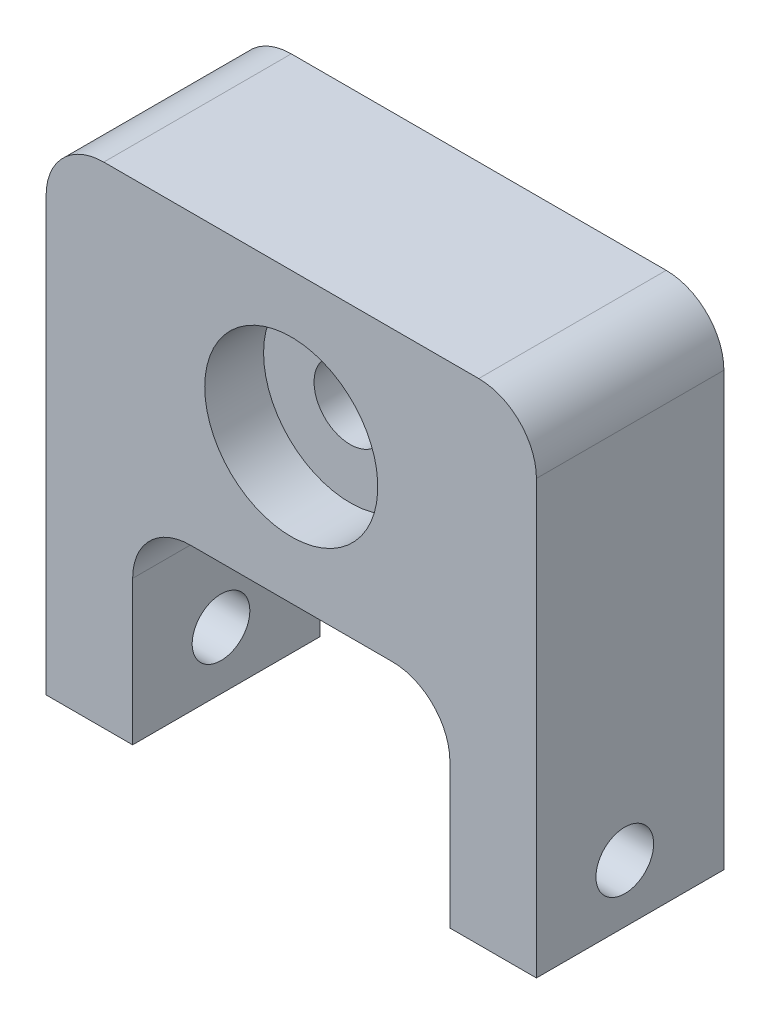
SolidWorks part; units mm, degrees
material "1060 Alloy"
ref_plane "Front" through (0, 0, 0) normal (0, 0, 1) x (1, 0, 0)
ref_plane "Top" through (0, 0, 0) normal (0, 1, 0) x (1, 0, 0)
ref_plane "Right" through (0, 0, 0) normal (1, 0, 0) x (0, 0, -1)
sketch "Sketch1" plane through (0, 0, 0) normal (0, 0, 1) x (1, 0, 0)
  line L1 (26.9875, -15.875) -> (-26.9875, -15.875)
  line L2 (26.9875, -15.875) -> (26.9875, 15.875)
  line L3 (26.9875, 15.875) -> (-26.9875, 15.875)
  line L4 (-26.9875, -15.875) -> (-26.9875, 15.875)
  line L5 (26.9875, -15.875) -> (-26.9875, 15.875) construction
  line L6 (26.9875, 15.875) -> (-26.9875, -15.875) construction
  point P0 (0, 0)
  dimension "D1" = 31.75
  dimension "D2" = 53.975
extrude "Boss-Extrude1" add sketch "Sketch1" along normal blind 20.6375
sketch "Sketch2" plane through (0, 0, 0) normal (0, 0, -1) x (-1, 0, 0)
  circle A0 centre (0, 0) radius 11.1125
  dimension "D1" = 22.225
extrude "Cut-Extrude1" cut sketch "Sketch2" against normal blind 6.985
sketch "Sketch3" plane through (0, 0, 6.985) normal (0, 0, -1) x (-1, 0, 0)
  circle A0 centre (0, 0) radius 8.255
  dimension "D1" = 16.51
extrude "Cut-Extrude2" cut sketch "Sketch3" against normal blind 2.413
sketch "Sketch4" plane through (0, 0, 9.398) normal (0, 0, -1) x (-1, 0, 0)
  circle A0 centre (0, 0) radius 3.9688
  dimension "D1" = 7.9375
extrude "Cut-Extrude3" cut sketch "Sketch4" against normal through all
sketch "Sketch6" plane through (0, 0, 9.398) normal (0, 0, -1) x (-1, 0, 0)
  circle A0 centre (0, 0) radius 9.525
  dimension "D1" = 19.05
extrude "Cut-Extrude4" cut sketch "Sketch6" against normal through all from offset 4.7625 offset against normal yes
sketch "Sketch7" plane through (0, -15.875, 0) normal (0, -1, 0) x (1, 0, 0)
  line L0 (-26.9875, 0) -> (26.9875, 0) construction
  line L1 (-26.9875, 20.6375) -> (-17.4625, 20.6375)
  line L2 (-26.9875, 20.6375) -> (-26.9875, 0)
  line L3 (-26.9875, 0) -> (-17.4625, 0)
  line L4 (-17.4625, 20.6375) -> (-17.4625, 0)
  line L6 (26.9875, 20.6375) -> (17.4625, 20.6375)
  line L7 (26.9875, 20.6375) -> (26.9875, 0)
  line L8 (26.9875, 0) -> (17.4625, 0)
  line L9 (17.4625, 20.6375) -> (17.4625, 0)
  dimension "D1" = 9.525
extrude "Boss-Extrude2" add sketch "Sketch7" along normal blind 22.225
sketch "Sketch9" plane through (26.9875, 0, 0) normal (1, 0, 0) x (0, 0, -1)
  line L0 (0, -38.1) -> (-20.6375, -38.1) construction
  circle A0 centre (-10.9095, -31.75) radius 3.175
  dimension "D2" = 6.35
  dimension "D1" = 6.35
extrude "Cut-Extrude5" cut sketch "Sketch9" against normal through all
fillet "Fillet1" radius 6.35 4 edges at (26.9875, 15.875, 10.3187) (-26.9875, 15.875, 10.3187) (17.4625, -15.875, 10.3187) (-17.4625, -15.875, 10.3187)
